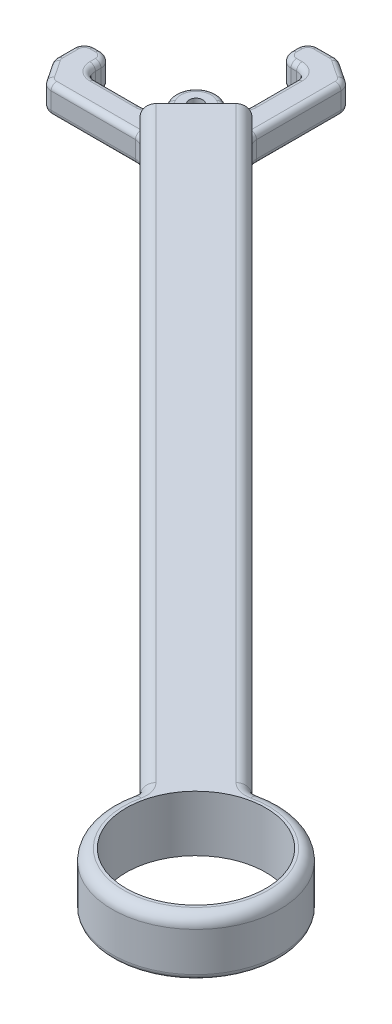
SolidWorks part; units mm, degrees
ref_plane "Front Plane" through (0, 0, 0) normal (0, 0, 1) x (1, 0, 0)
ref_plane "Top Plane" through (0, 0, 0) normal (0, 1, 0) x (1, 0, 0)
ref_plane "Right Plane" through (0, 0, 0) normal (1, 0, 0) x (0, 0, -1)
sketch "Sketch1" plane through (0, 0, 0) normal (0, 1, 0) x (1, 0, 0)
  line L2 (-20, 13.3462) -> (-20, 7.8462)
  line L3 (-17, 3.3462) -> (0, 3.3462)
  line L4 (0, 33.3462) -> (5.5, 33.3462)
  line L5 (10, 30.3462) -> (10, 13.3462)
  line L6 (0, 3.3462) -> (106.066, -102.7198)
  line L7 (10, 13.3462) -> (116.066, -92.7198)
  line L8 (10, 13.3462) -> (0, 3.3462) construction
  line L9 (116.066, -92.7198) -> (106.066, -102.7198) construction
  line L10 (0, 13.3462) -> (135.1855, 13.3462) construction
  line L11 (0, 33.3462) -> (0, 28.3462)
  line L12 (-20, 13.3462) -> (-15, 13.3462)
  line L13 (0, 28.3462) -> (5, 28.3462)
  line L14 (-2.6163, 10.7299) -> (-0.2326, 8.3462)
  line L15 (5, 28.3462) -> (5, 13.5788)
  line L16 (5, 13.5788) -> (2.6163, 15.9625)
  line L17 (-15, 13.3462) -> (-15, 8.3462)
  line L18 (-15, 8.3462) -> (-0.2326, 8.3462)
  line L19 (0, 13.3462) -> (0, -90.5549) construction
  line L20 (5.5, 33.3462) -> (10, 30.3462)
  line L21 (9.2226, 30.8644) -> (7.5, 32.0129) construction
  line L22 (-20, 7.8462) -> (-17, 3.3462)
  line L23 (-18.6667, 5.8462) -> (-17.5182, 4.1235) construction
  arc A0 (106.066, -102.7198) -> (116.066, -92.7198) centre (120.4202, -107.074) ccw
  circle A1 centre (120.4202, -107.074) radius 12.5
  circle A6 centre (0, 13.3462) radius 1.2 construction
  circle A7 centre (0, 13.3462) radius 1.2
  arc A8 (2.6163, 15.9625) -> (-2.6163, 10.7299) centre (0, 13.3462) ccw
  circle A9 centre (0, 13.3462) radius 3.7 construction
  point P7 (0, 0)
  point P26 (0, 0)
  dimension "D9" = 30
  dimension "D7" = 25
  dimension "D6" = 45
  dimension "D8" = 150
  dimension "D1" = 30
  dimension "D3" = 30
  dimension "D11" = 5
  dimension "D12" = 5
  dimension "D13" = 5
  dimension "D14" = 5
  dimension "D2" = 10
  dimension "D4" = 10
  dimension "D10" = 2.5
extrude "Boss-Extrude1" add sketch "Sketch1" along normal blind 10
sketch "Sketch2" plane through (0, 10, 0) normal (0, 1, 0) x (1, 0, 0)
  line L2 (-15, 13.3462) -> (-20, 13.3462) construction
  line L16 (0, 33.3462) -> (0, 28.3462) construction
  line L17 (-15, 13.3462) -> (-20, 13.3462)
  line L18 (0, 33.3462) -> (0, 28.3462)
  line L19 (0, 28.3462) -> (5, 28.3462) construction
  line L20 (5, 28.3462) -> (5, 13.5788) construction
  line L21 (5, 13.5788) -> (2.6163, 15.9625) construction
  line L22 (-2.6163, 10.7299) -> (-0.2326, 8.3462) construction
  line L23 (-0.2326, 8.3462) -> (-15, 8.3462) construction
  line L24 (-15, 8.3462) -> (-15, 13.3462) construction
  line L25 (0, 28.3462) -> (5, 28.3462)
  line L26 (5, 28.3462) -> (5, 13.5788)
  line L27 (5, 13.5788) -> (2.6163, 15.9625)
  line L28 (-2.6163, 10.7299) -> (-0.2326, 8.3462)
  line L29 (-0.2326, 8.3462) -> (-15, 8.3462)
  line L30 (-15, 8.3462) -> (-15, 13.3462)
  line L31 (10, 13.3462) -> (0, 3.3462)
  line L32 (-20, 13.3462) -> (-20, 7.8462) construction
  line L33 (-20, 7.8462) -> (-17, 3.3462) construction
  line L34 (-17, 3.3462) -> (0, 3.3462) construction
  line L35 (10, 13.3462) -> (10, 30.3462) construction
  line L36 (10, 30.3462) -> (5.5, 33.3462) construction
  line L37 (5.5, 33.3462) -> (0, 33.3462) construction
  line L38 (5.5, 33.3462) -> (0, 33.3462)
  line L39 (10, 30.3462) -> (5.5, 33.3462)
  line L40 (10, 13.3462) -> (10, 30.3462)
  line L41 (-17, 3.3462) -> (0, 3.3462)
  line L42 (-20, 7.8462) -> (-17, 3.3462)
  line L43 (-20, 13.3462) -> (-20, 7.8462)
  arc A2 (2.6163, 15.9625) -> (-2.6163, 10.7299) centre (0, 13.3462) ccw construction
  arc A3 (2.6163, 15.9625) -> (-2.6163, 10.7299) centre (0, 13.3462) ccw
extrude "Cut-Extrude1" cut sketch "Sketch2" against normal blind 5
fillet "Fillet1" radius 2 19 edges at (106.066, 5, 102.7198) (116.066, 5, 92.7198) (10, 2.5, -13.3462) (0, 2.5, -3.3462) (-20, 2.5, -13.3462) (0, 2.5, -33.3462) (53.033, 10, 49.6868) (131.0268, 10, 117.6806) (63.033, 10, 39.6868) (-15, 2.5, -13.3462) (0, 2.5, -28.3462) (5, 2.5, -28.3462) (-15, 2.5, -8.3462) (-0.2326, 2.5, -8.3462) (5, 2.5, -13.5788) (-20, 2.5, -7.8462) (-17, 2.5, -3.3462) (5.5, 2.5, -33.3462) (10, 2.5, -30.3462)
fillet "Fillet2" radius 1 59 edges at (-0.0631, 5, -3.1939) (10.1522, 5, -13.4092) (-8.379, 5, -3.3462) (10, 5, -21.7252) (10, 0, -21.7252) (10.1522, 0, -13.4092) (62.9197, 0, 39.5735) (116.1124, 0, 92.4146) (131.0268, 0, 117.6806) (105.7608, 0, 102.7662) (52.9197, 0, 49.5735) (-0.0631, 0, -3.1939) (-8.379, 0, -3.3462) (-20, 0, -9.899) (-19.4142, 0, -12.7604) (-17.5, 0, -13.3462) (0, 0, -30.8462) (0.5858, 0, -32.7604) (3.4472, 0, -33.3462) (-20, 5, -9.899) (-19.4142, 5, -12.7604) (-17.5, 5, -13.3462) (0, 5, -30.8462) (0.5858, 5, -32.7604) (3.4472, 5, -33.3462) (-15.5858, 0, -12.7604) (-15, 0, -10.8462) (-14.4142, 0, -8.932) (-8.9233, 0, -8.3462) (-3.0995, 0, -9.3729) (-2.6163, 0, -15.9625) (3.9733, 0, -16.4457) (5, 0, -22.2695) (4.4142, 0, -27.7604) (2.5, 0, -28.3462) (0.5858, 0, -28.932) (-15.5858, 5, -12.7604) (-15, 5, -10.8462) (-14.4142, 5, -8.932) (-8.9233, 5, -8.3462) (-3.0995, 5, -9.3729) (-2.6163, 5, -15.9625) (3.9733, 5, -16.4457) (5, 5, -22.2695) (4.4142, 5, -27.7604) (2.5, 5, -28.3462) (0.5858, 5, -28.932) (5.474, 0, -33.2604) (7.5566, 0, -31.9751) (9.7633, 0, -30.2195) (-16.8733, 0, -3.5828) (-18.6289, 0, -5.7896) (-19.9142, 0, -7.8722) (-16.8733, 5, -3.5828) (-18.6289, 5, -5.7896) (-19.9142, 5, -7.8722) (5.474, 5, -33.2604) (7.5566, 5, -31.9751) (9.7633, 5, -30.2195)
equation "\"motor sweep\"= 45"
equation "\"D6@Sketch1\"=\"motor sweep\""
equation "\"l\"= 15"
equation "\"D8@Sketch1\"=\"l\""
